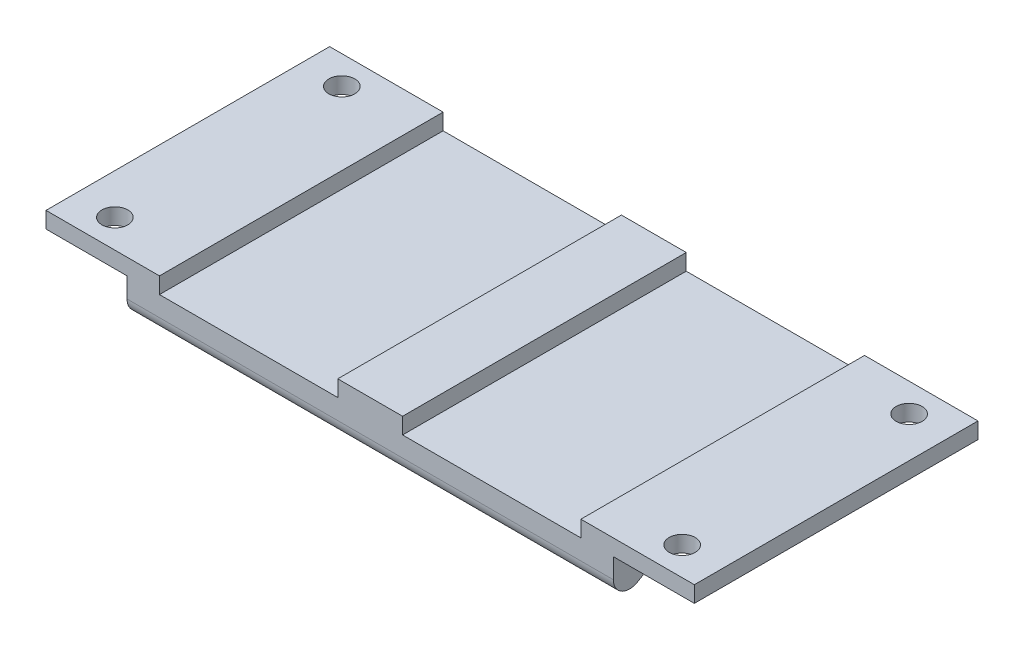
SolidWorks part; units mm, degrees
material "PEI"
ref_plane "Front Plane" through (0, 0, 0) normal (0, 0, 1) x (1, 0, 0)
ref_plane "Top Plane" through (0, 0, 0) normal (0, 1, 0) x (1, 0, 0)
ref_plane "Right Plane" through (0, 0, 0) normal (1, 0, 0) x (0, 0, -1)
sketch "Sketch1" plane through (0, 0, 0) normal (0, 1, 0) x (1, 0, 0)
  line L1 (30, -17.5) -> (-30, -17.5)
  line L2 (30, -17.5) -> (30, 17.5)
  line L3 (30, 17.5) -> (-30, 17.5)
  line L4 (-30, -17.5) -> (-30, 17.5)
  line L5 (30, -17.5) -> (-30, 17.5) construction
  line L6 (30, 17.5) -> (-30, -17.5) construction
  point P0 (0, 0)
  dimension "D1" = 35
  dimension "D2" = 60
extrude "Boss-Extrude1" add sketch "Sketch1" against normal blind 8
sketch "Sketch2" plane through (30, 0, 0) normal (1, 0, 0) x (0, 0, -1)
  line L0 (-17.5, -8) -> (-12.5, -5)
  line L1 (-12.5, -5) -> (12.5, -5)
  line L2 (0, -5) -> (0, -8)
  line L3 (17.5, -8) -> (12.5, -5)
  line L4 (17.5, 0) -> (-17.5, 0)
  line L5 (-17.5, 0) -> (-17.5, -8)
  line L6 (-17.5, -8) -> (17.5, -8)
  line L7 (17.5, -8) -> (17.5, 0)
  line L8 (17.5, 0) -> (-17.5, 0)
  line L9 (-17.5, 0) -> (-17.5, -8)
  line L10 (-17.5, -8) -> (17.5, -8)
  line L11 (17.5, -8) -> (17.5, 0)
  line M7 (-17.5, -8) -> (17.5, -8)
  dimension "D2" = 5
  dimension "D3" = 3
  dimension "D1" = 0
extrude "Cut-Extrude1" cut sketch "Sketch2" against normal through all and the other way through all contours L2 L1 L0 M7 | L3 L1 L2 M7 region at (30, -6.5833, 7.5694) region at (30, -6.5833, -7.5694)
fillet "Fillet1" radius 2 4 edges at (0, -5, 12.5) (0, -5, -12.5) (0, -8, -17.5) (0, -8, 17.5)
sketch "Sketch3" plane through (0, 0, 17.5) normal (0, 0, 1) x (1, 0, 0)
  line L0 (-30, 0) -> (30, 0) construction
  line L1 (-26, 2) -> (-4, 2)
  line L2 (-26, 2) -> (-26, -2)
  line L3 (-26, -2) -> (-4, -2)
  line L4 (-30, 0) -> (-30, -4.4676)
  line L5 (-30, -4.4676) -> (30, -4.4676)
  line L6 (30, -4.4676) -> (30, 0)
  line L7 (30, 0) -> (-30, 0)
  line L8 (-30, 0) -> (-30, -4.4676)
  line L9 (-30, -4.4676) -> (30, -4.4676)
  line L10 (30, -4.4676) -> (30, 0)
  line L11 (30, 0) -> (-30, 0)
  line L12 (-4, 2) -> (-4, -2)
  line L13 (-26, 2) -> (-4, -2) construction
  line L14 (-26, -2) -> (-4, 2) construction
  line L15 (0, 0) -> (0, -4.4676)
  line L16 (26, -2) -> (4, 2) construction
  line L17 (26, 2) -> (4, -2) construction
  line L18 (4, 2) -> (4, -2)
  line L19 (26, -2) -> (4, -2)
  line L20 (26, 2) -> (26, -2)
  line L21 (26, 2) -> (4, 2)
  point P2 (-15, 0)
  point P13 (0, 0)
  point P18 (15, 0)
  dimension "D2" = 22
  dimension "D3" = 4
  dimension "D4" = 15
  dimension "D1" = 0
extrude "Cut-Extrude2" cut sketch "Sketch3" against normal through all contours L12 L11 L2 L3 | L20 L11 L18 L19 region at (-15, -1, 17.5) region at (15, -1, 17.5)
sketch "Sketch5" plane through (-30, 0, 0) normal (-1, 0, 0) x (0, 0, 1)
  line L1 (-17.5, 0) -> (17.5, 0)
  line L2 (-17.5, 0) -> (-17.5, -2)
  line L3 (-17.5, -2) -> (17.5, -2)
  line L4 (17.5, 0) -> (17.5, -2)
  line L6 (-17.5, 0) -> (-17.5, -4.4676)
  line L7 (-14.471, -6.1826) -> (-12.975, -5.285)
  line L8 (-11.946, -5) -> (11.946, -5)
  line L9 (12.975, -5.285) -> (14.471, -6.1826)
  line L10 (17.5, -4.4676) -> (17.5, 0)
  line L11 (17.5, 0) -> (-17.5, 0)
  line L12 (-17.5, 0) -> (-17.5, -4.4676)
  line L13 (-14.471, -6.1826) -> (-12.975, -5.285)
  line L14 (-11.946, -5) -> (11.946, -5)
  line L15 (12.975, -5.285) -> (14.471, -6.1826)
  line L16 (17.5, -4.4676) -> (17.5, 0)
  line L17 (17.5, 0) -> (-17.5, 0)
  arc A4 (-17.5, -4.4676) -> (-14.471, -6.1826) centre (-15.5, -4.4676) ccw
  arc A5 (-11.946, -5) -> (-12.975, -5.285) centre (-11.946, -7) ccw
  arc A6 (12.975, -5.285) -> (11.946, -5) centre (11.946, -7) ccw
  arc A7 (14.471, -6.1826) -> (17.5, -4.4676) centre (15.5, -4.4676) ccw
  arc A8 (-17.5, -4.4676) -> (-14.471, -6.1826) centre (-15.5, -4.4676) ccw
  arc A9 (-11.946, -5) -> (-12.975, -5.285) centre (-11.946, -7) ccw
  arc A10 (12.975, -5.285) -> (11.946, -5) centre (11.946, -7) ccw
  arc A11 (14.471, -6.1826) -> (17.5, -4.4676) centre (15.5, -4.4676) ccw
  line M13 (-17.5, 0) -> (-17.5, -4.4676)
  line M21 (17.5, -4.4676) -> (17.5, 0)
  line M22 (17.5, 0) -> (-17.5, 0)
  dimension "D2" = 2
  dimension "D1" = 0
extrude "Boss-Extrude2" add sketch "Sketch5" along normal blind 10 contours L3 M13 M21 M22 region at (-30, -1, 0)
mirror "Mirror1" about plane through (0, 0, 0) normal (1, 0, 0) of "Boss-Extrude2"
sketch "Sketch6" plane through (0, 0, 0) normal (0, 1, 0) x (1, 0, 0)
  line L0 (0, 0) -> (0, 14)
  line L1 (0, 14) -> (-35, 14)
  line L2 (0, 0) -> (-40, 0)
  line L4 (-26, -17.5) -> (-26, 17.5)
  line L5 (-26, 17.5) -> (-40, 17.5)
  line L6 (-40, 17.5) -> (-40, -17.5)
  line L7 (-40, -17.5) -> (-26, -17.5)
  line L8 (-26, -17.5) -> (-26, 17.5)
  line L9 (-26, 17.5) -> (-40, 17.5)
  line L10 (-40, 17.5) -> (-40, -17.5)
  line L11 (-40, -17.5) -> (-26, -17.5)
  line L12 (-26, -17.5) -> (-4, -17.5)
  line L13 (-4, -17.5) -> (-4, 17.5)
  line L14 (-4, 17.5) -> (-26, 17.5)
  line L15 (-26, 17.5) -> (-26, -17.5)
  line L16 (-26, -17.5) -> (-4, -17.5)
  line L17 (-4, -17.5) -> (-4, 17.5)
  line L18 (-4, 17.5) -> (-26, 17.5)
  line L19 (-26, 17.5) -> (-26, -17.5)
  line L20 (4, 17.5) -> (-4, 17.5)
  line L21 (-4, 17.5) -> (-4, -17.5)
  line L22 (-4, -17.5) -> (4, -17.5)
  line L23 (4, -17.5) -> (4, 17.5)
  line L24 (4, 17.5) -> (-4, 17.5)
  line L25 (-4, 17.5) -> (-4, -17.5)
  line L26 (-4, -17.5) -> (4, -17.5)
  line L27 (4, -17.5) -> (4, 17.5)
  line L28 (4, -17.5) -> (26, -17.5)
  line L29 (26, -17.5) -> (26, 17.5)
  line L30 (26, 17.5) -> (4, 17.5)
  line L31 (4, 17.5) -> (4, -17.5)
  line L32 (4, -17.5) -> (26, -17.5)
  line L33 (26, -17.5) -> (26, 17.5)
  line L34 (26, 17.5) -> (4, 17.5)
  line L35 (4, 17.5) -> (4, -17.5)
  line L36 (40, 17.5) -> (26, 17.5)
  line L37 (26, 17.5) -> (26, -17.5)
  line L38 (26, -17.5) -> (40, -17.5)
  line L39 (40, -17.5) -> (40, 17.5)
  line L40 (40, 17.5) -> (26, 17.5)
  line L41 (26, 17.5) -> (26, -17.5)
  line L42 (26, -17.5) -> (40, -17.5)
  line L43 (40, -17.5) -> (40, 17.5)
  circle A0 centre (-35, 14) radius 1.6
  circle A1 centre (35, 14) radius 1.6
  circle A2 centre (35, -14) radius 1.6
  circle A3 centre (-35, -14) radius 1.6
  dimension "D8" = 3.2
  dimension "D6" = 14
  dimension "D7" = 35
  dimension "D1" = 0
  dimension "D2" = 0
  dimension "D3" = 0
  dimension "D4" = 0
  dimension "D5" = 0
extrude "Cut-Extrude3" cut sketch "Sketch6" against normal blind 10 contours A0 | A3 | A1 | A2 region at (-36.5547, 0, -14) region at (35, 0, -14) region at (35, 0, 14) region at (-35, 0, 14)
